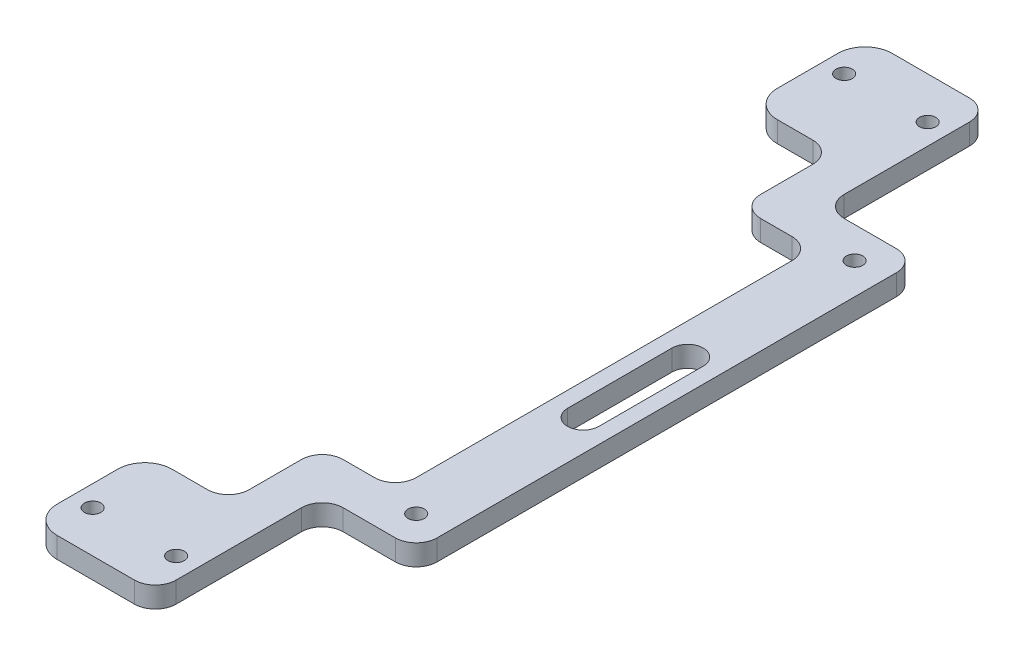
SolidWorks part; units mm, degrees
material "PC High Viscosity"
ref_plane "Front Plane" through (0, 0, 0) normal (0, 0, 1) x (1, 0, 0)
ref_plane "Top Plane" through (0, 0, 0) normal (0, 1, 0) x (1, 0, 0)
ref_plane "Right Plane" through (0, 0, 0) normal (1, 0, 0) x (0, 0, -1)
sketch "Sketch1" plane through (0, 0, 0) normal (0, 1, 0) x (1, 0, 0)
  line L0 (0, 0) -> (0, 50.8)
  line L5 (0, 50.8) -> (-28.575, 50.8)
  line L6 (-28.575, 50.8) -> (-28.575, 203.2)
  line L7 (-28.575, 203.2) -> (0, 203.2)
  line L8 (0, 203.2) -> (0, 254)
  line L9 (0, 254) -> (203.2, 254)
  line L10 (203.2, 254) -> (203.2, 203.2)
  line L11 (203.2, 203.2) -> (231.775, 203.2)
  line L12 (231.775, 203.2) -> (231.775, 50.8)
  line L13 (231.775, 50.8) -> (203.2, 50.8)
  line L14 (203.2, 50.8) -> (203.2, 0)
  line L15 (203.2, 0) -> (0, 0)
  line L16 (101.6, 219.075) -> (101.6, 34.925) construction
  line L17 (12.7, 219.075) -> (190.5, 219.075)
  line L18 (12.7, 219.075) -> (12.7, 34.925)
  line L19 (12.7, 34.925) -> (190.5, 34.925)
  line L20 (190.5, 219.075) -> (190.5, 34.925)
  line L21 (-9.525, 63.5) -> (12.7, 63.5)
  line L22 (-9.525, 63.5) -> (-9.525, 190.5)
  line L23 (-9.525, 190.5) -> (12.7, 190.5)
  line L24 (12.7, 63.5) -> (12.7, 190.5)
  line L25 (212.725, 190.5) -> (190.5, 190.5)
  line L26 (190.5, 63.5) -> (190.5, 190.5)
  line L27 (212.725, 63.5) -> (190.5, 63.5)
  line L28 (212.725, 63.5) -> (212.725, 190.5)
  line L29 (12.7, 127) -> (-9.525, 127) construction
  line L30 (-19.05, 111.125) -> (-19.05, 142.875) construction
  line L31 (-23.8125, 111.125) -> (-23.8125, 142.875)
  line L32 (-14.2875, 111.125) -> (-14.2875, 142.875)
  line L33 (222.25, 111.125) -> (222.25, 142.875) construction
  line L34 (227.0125, 111.125) -> (227.0125, 142.875)
  line L35 (217.4875, 111.125) -> (217.4875, 142.875)
  line L36 (12.7, 219.075) -> (12.7, 254) construction
  line L37 (12.7, 34.925) -> (12.7, 0) construction
  circle A0 centre (196.85, 241.3) radius 2.4892
  circle A1 centre (196.85, 12.7) radius 2.4892
  arc A2 (-23.8125, 111.125) -> (-14.2875, 111.125) centre (-19.05, 111.125) ccw
  arc A3 (-14.2875, 142.875) -> (-23.8125, 142.875) centre (-19.05, 142.875) ccw
  arc A4 (227.0125, 111.125) -> (217.4875, 111.125) centre (222.25, 111.125) cw
  arc A5 (217.4875, 142.875) -> (227.0125, 142.875) centre (222.25, 142.875) cw
  point P34 (-19.05, 127)
  point P44 (222.25, 127)
  dimension "D10" = 4.9784
  dimension "D1" = 177.8
  dimension "D5" = 12.7
  dimension "D6" = 12.7
  dimension "D7" = 152.4
  dimension "D8" = 22.225
  dimension "D9" = 19.05
  dimension "D11" = 12.7
  dimension "D12" = 12.7
  dimension "D13" = 6.35
  dimension "D14" = 12.7
  dimension "D15" = 9.525
  dimension "D16" = 9.525
  dimension "D17" = 31.75
  dimension "D2" = 254
  dimension "D3" = 184.15
extrude "Boss-Extrude1" add sketch "Sketch1" along normal mid plane 6.35 contours L15 L14 L13 L12 L11 L10 L9 L8 L7 L6 L5 L0 A1 A0 L28 L27 L20 L19 L18 L21 L22 L23 L17 L25 region at (3.6373, 0, -25.4)
fillet "Fillet1" radius 6.35 24 edges at (0, 0, 0) (0, 0, -50.8) (-28.575, 0, -50.8) (-28.575, 0, -203.2) (0, 0, -203.2) (0, 0, -254) (203.2, 0, -254) (203.2, 0, -203.2) (231.775, 0, -203.2) (231.775, 0, -50.8) (203.2, 0, -50.8) (203.2, 0, 0) (212.725, 0, -190.5) (190.5, 0, -190.5) (190.5, 0, -219.075) (12.7, 0, -219.075) (-9.525, 0, -190.5) (-9.525, 0, -63.5) (12.7, 0, -63.5) (12.7, 0, -34.925) (190.5, 0, -34.925) (190.5, 0, -63.5) (212.725, 0, -63.5) (12.7, 0, -190.5)
pattern_linear "LPattern1" count 8 spacing 25.4 along (-1, 0, 0) of face at (196.85, 3.175, -238.8108) of face at (196.85, 3.175, -10.2108)
sketch "Sketch2" plane through (0, 3.175, 0) normal (0, 1, 0) x (1, 0, 0)
  line L0 (6.35, 254) -> (196.85, 254) construction
  line L1 (165.1, 254) -> (-28.575, 254)
  line L2 (165.1, 254) -> (165.1, 0)
  line L3 (165.1, 0) -> (-28.575, 0)
  line L4 (-28.575, 254) -> (-28.575, 0)
  line L5 (196.85, 0) -> (6.35, 0) construction
  line L6 (-28.575, 57.15) -> (-28.575, 196.85) construction
  line L7 (222.25, 193.675) -> (222.25, 60.325) construction
  line L9 (217.4875, 111.125) -> (217.4875, 142.875) construction
  line L10 (209.55, 203.2) -> (225.425, 203.2) construction
  circle A1 centre (171.45, 241.3) radius 2.4892 construction
  circle A2 centre (222.25, 193.675) radius 2.4892
  circle A3 centre (222.25, 60.325) radius 2.4892
  arc A4 (227.0125, 142.875) -> (217.4875, 142.875) centre (222.25, 142.875) ccw construction
  point P16 (222.25, 127)
  point P17 (217.4875, 127)
  point P18 (0, 0)
  point P26 (222.25, 147.6375)
  dimension "D1" = 6.35
  dimension "D2" = 4.9784
  dimension "D3" = 9.525
extrude "Cut-Extrude1" cut sketch "Sketch2" against normal through all
fillet "Fillet2" radius 8.255 4 edges at (165.1, 0, -219.075) (165.1, 0, -254) (165.1, 0, 0) (165.1, 0, -34.925)
equation "\"D6@Sketch1\"=\"D5@Sketch1\""
equation "\"D14@Sketch1\"=\"D5@Sketch1\""
